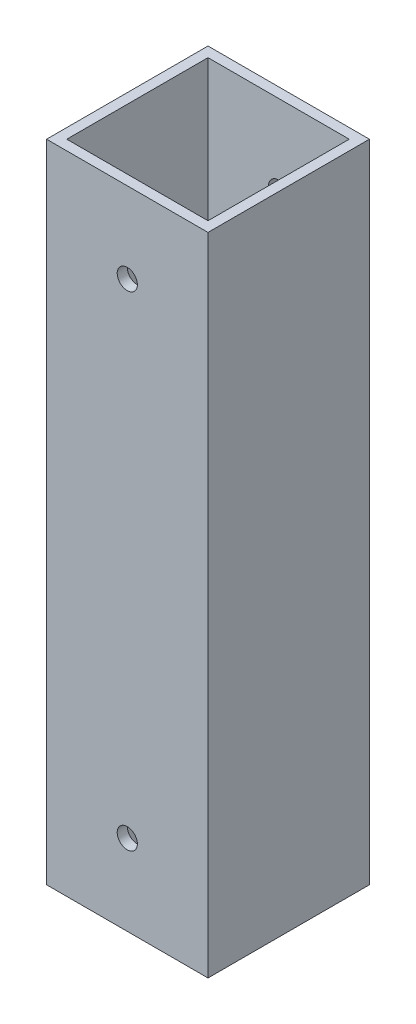
SolidWorks part; units mm, degrees
ref_plane "Front Plane" through (0, 0, 0) normal (0, 0, 1) x (1, 0, 0)
ref_plane "Top Plane" through (0, 0, 0) normal (0, 1, 0) x (1, 0, 0)
ref_plane "Right Plane" through (0, 0, 0) normal (1, 0, 0) x (0, 0, -1)
sketch "Sketch1" plane through (0, 0, 0) normal (0, 1, 0) x (1, 0, 0)
  line L1 (-12.7, -12.7) -> (12.7, -12.7)
  line L2 (-12.7, -12.7) -> (-12.7, 12.7)
  line L3 (-12.7, 12.7) -> (12.7, 12.7)
  line L4 (12.7, -12.7) -> (12.7, 12.7)
  line L5 (-12.7, -12.7) -> (12.7, 12.7) construction
  line L6 (-12.7, 12.7) -> (12.7, -12.7) construction
  line L7 (-11.1125, -11.1125) -> (11.1125, -11.1125)
  line L8 (-11.1125, -11.1125) -> (-11.1125, 11.1125)
  line L9 (-11.1125, 11.1125) -> (11.1125, 11.1125)
  line L10 (11.1125, -11.1125) -> (11.1125, 11.1125)
  line L11 (-11.1125, -11.1125) -> (11.1125, 11.1125) construction
  line L12 (-11.1125, 11.1125) -> (11.1125, -11.1125) construction
  point P0 (0, 0)
  point P6 (0, 0)
  dimension "D1" = 25.4
  dimension "D2" = 1.5875
extrude "Boss-Extrude1" add sketch "Sketch1" along normal blind 101.6
sketch "Sketch2" plane through (0, 0, -12.7) normal (0, 0, -1) x (-1, 0, 0)
  line L0 (0, 0) -> (0, 101.6) construction
  line L1 (-12.7, 0) -> (12.7, 0) construction
  line L2 (-12.7, 101.6) -> (12.7, 101.6) construction
  circle A0 centre (0, 88.9) radius 1.5875
  circle A1 centre (0, 12.7) radius 1.5875
  dimension "D3" = 3.175
  dimension "D1" = 12.7
  dimension "D2" = 12.7
extrude "Cut-Extrude1" cut sketch "Sketch2" against normal up to surface (25.4 mm away) up to face at (0, 50.8, 12.7)
